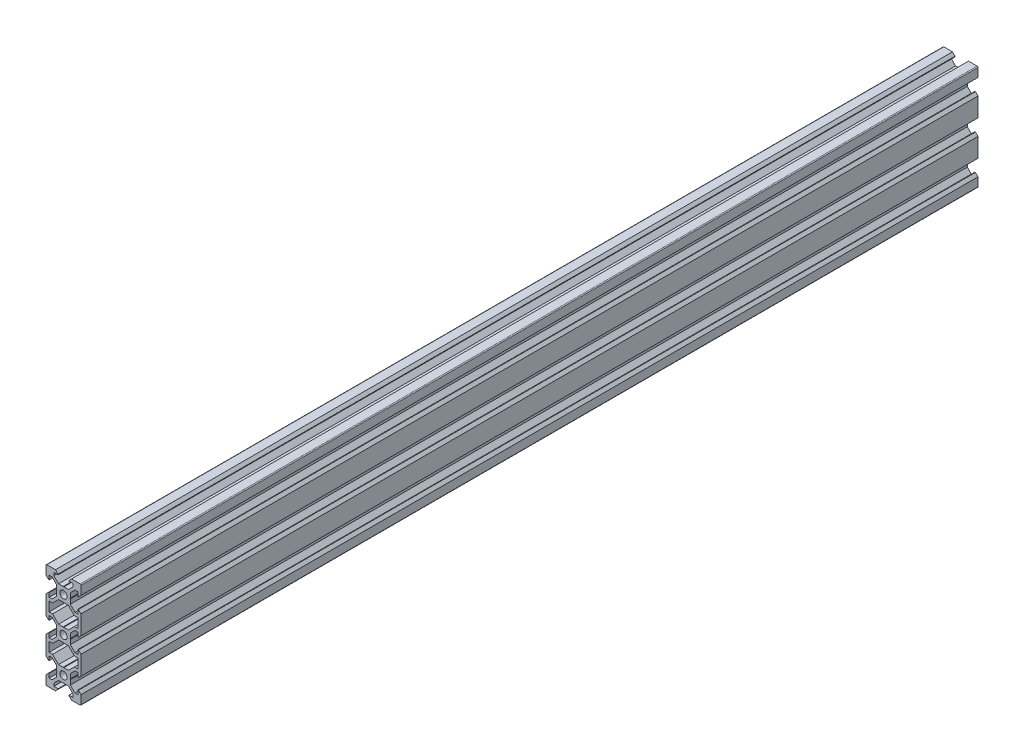
SolidWorks part; units mm, degrees
ref_plane "Plan de face" through (0, 0, 0) normal (0, 0, 1) x (1, 0, 0)
ref_plane "Plan de dessus" through (0, 0, 0) normal (0, 1, 0) x (1, 0, 0)
ref_plane "Plan de droite" through (0, 0, 0) normal (1, 0, 0) x (0, 0, -1)
ref_axis "Axe" through (0, 0, -13.782) along (0, 0, 1)
sketch "Esquisse1" plane through (0, 0, 0) normal (0, 0, 1) x (1, 0, 0)
  line L0 (0, 27.6392) -> (0, -27.6392) construction
  line L1 (-33.6074, 0) -> (33.6074, 0) construction
  line L2 (0, 0) -> (-22.2114, 22.2114) construction
  line L3 (-9.5, 10) -> (-4.58, 10)
  line L4 (-4.58, 10) -> (-3.125, 8.545)
  line L5 (-3.125, 8.545) -> (-3.125, 8.2)
  line L6 (-3.125, 8.2) -> (-5.5, 8.2)
  line L7 (-2.8393, 3.9) -> (-5.5, 6.5607)
  line L8 (-2.8393, 3.9) -> (-0.21, 3.9)
  line L9 (-5.5, 6.5607) -> (-5.5, 8.2)
  line L10 (0, 3.69) -> (0, 2.1)
  line L11 (-3.9, 2.8393) -> (-6.5607, 5.5)
  line L12 (-8.545, 3.125) -> (-8.2, 3.125)
  line L13 (-8.2, 3.125) -> (-8.2, 5.5)
  line L14 (-6.5607, 5.5) -> (-8.2, 5.5)
  line L15 (-10, 4.58) -> (-8.545, 3.125)
  line L16 (-10, 9.5) -> (-10, 4.58)
  line L17 (-0.21, 3.9) -> (0, 3.69)
  line L18 (-3.9, 2.8393) -> (-3.9, 0.21)
  line L19 (-6.2393, -12.7) -> (-8.2, -12.7)
  line L20 (-3.9, 0.21) -> (-3.69, 0)
  line L21 (-0.21, -3.9) -> (0, -3.69)
  line L22 (0, -3.69) -> (0, -2.1)
  line L23 (-6.5607, -5.5) -> (-8.2, -5.5)
  line L24 (-2.8393, -3.9) -> (-0.21, -3.9)
  line L25 (-8.545, -3.125) -> (-8.2, -3.125)
  line L26 (-10, -4.58) -> (-8.545, -3.125)
  line L27 (-8.2, -3.125) -> (-8.2, -5.5)
  line L28 (-2.8393, -3.9) -> (-6.2393, -7.3)
  line L29 (-3.9, -2.8393) -> (-6.5607, -5.5)
  line L30 (-3.9, -2.8393) -> (-3.9, -0.21)
  line L31 (-3.9, -0.21) -> (-3.69, 0)
  line L32 (-6.2393, -7.3) -> (-8.2, -7.3)
  line L33 (-8.2, -7.3) -> (-8.2, -12.7)
  line L34 (-8.2, -10) -> (-10, -10) construction
  line L35 (-10, -15.42) -> (-10, -4.58)
  line L36 (-3.9, -19.79) -> (-3.69, -20)
  line L37 (-3.9, -17.1607) -> (-3.9, -19.79)
  line L38 (-3.9, -17.1607) -> (-6.5607, -14.5)
  line L39 (-2.8393, -16.1) -> (-6.2393, -12.7)
  line L40 (-8.2, -16.875) -> (-8.2, -14.5)
  line L41 (-10, -15.42) -> (-8.545, -16.875)
  line L42 (-8.545, -16.875) -> (-8.2, -16.875)
  line L43 (-2.8393, -16.1) -> (-0.21, -16.1)
  line L44 (-6.5607, -14.5) -> (-8.2, -14.5)
  line L45 (0, -16.31) -> (0, -17.9)
  line L46 (-0.21, -16.1) -> (0, -16.31)
  line L47 (-8.2, -30) -> (-10, -30) construction
  line L48 (-3.69, -20) -> (0, -20) construction
  line L49 (-0.21, -23.9) -> (0, -23.69)
  line L50 (0, -23.69) -> (0, -22.1)
  line L51 (-6.5607, -25.5) -> (-8.2, -25.5)
  line L52 (-2.8393, -23.9) -> (-0.21, -23.9)
  line L53 (-8.545, -23.125) -> (-8.2, -23.125)
  line L54 (-10, -24.58) -> (-8.545, -23.125)
  line L55 (-8.2, -23.125) -> (-8.2, -25.5)
  line L56 (-2.8393, -23.9) -> (-6.2393, -27.3)
  line L57 (-3.9, -22.8393) -> (-6.5607, -25.5)
  line L58 (-3.9, -22.8393) -> (-3.9, -20.21)
  line L59 (-3.9, -20.21) -> (-3.69, -20)
  line L60 (-10, -24.58) -> (-10, -35.42)
  line L61 (-8.2, -32.7) -> (-8.2, -27.3)
  line L62 (-6.2393, -32.7) -> (-8.2, -32.7)
  line L63 (-3.9, -39.79) -> (-3.69, -40)
  line L64 (-3.9, -37.1607) -> (-3.9, -39.79)
  line L65 (-3.9, -37.1607) -> (-6.5607, -34.5)
  line L66 (-2.8393, -36.1) -> (-6.2393, -32.7)
  line L67 (-8.2, -36.875) -> (-8.2, -34.5)
  line L68 (-10, -35.42) -> (-8.545, -36.875)
  line L69 (-8.545, -36.875) -> (-8.2, -36.875)
  line L70 (-2.8393, -36.1) -> (-0.21, -36.1)
  line L71 (-6.5607, -34.5) -> (-8.2, -34.5)
  line L72 (0, -36.31) -> (0, -37.9)
  line L73 (-0.21, -36.1) -> (0, -36.31)
  line L74 (-3.9, -40.21) -> (-3.69, -40)
  line L75 (-6.2393, -27.3) -> (-8.2, -27.3)
  line L76 (-3.9, -42.8393) -> (-3.9, -40.21)
  line L77 (-0.21, -43.9) -> (0, -43.69)
  line L78 (-10, -49.5) -> (-10, -44.58)
  line L79 (-10, -44.58) -> (-8.545, -43.125)
  line L80 (-6.5607, -45.5) -> (-8.2, -45.5)
  line L81 (-8.2, -43.125) -> (-8.2, -45.5)
  line L82 (-8.545, -43.125) -> (-8.2, -43.125)
  line L83 (-3.9, -42.8393) -> (-6.5607, -45.5)
  line L84 (0, -43.69) -> (0, -42.1)
  line L85 (-5.5, -46.5607) -> (-5.5, -48.2)
  line L86 (-2.8393, -43.9) -> (-0.21, -43.9)
  line L87 (-2.8393, -43.9) -> (-5.5, -46.5607)
  line L88 (-3.125, -48.2) -> (-5.5, -48.2)
  line L89 (-3.125, -48.545) -> (-3.125, -48.2)
  line L90 (-4.58, -50) -> (-3.125, -48.545)
  line L91 (-9.5, -50) -> (-4.58, -50)
  arc A0 (0, -2.1) -> (0, 2.1) centre (0, 0) cw
  arc A1 (-9.5, 10) -> (-10, 9.5) centre (-9.5, 9.5) ccw
  arc A2 (0, -37.9) -> (0, -42.1) centre (0, -40) ccw
  arc A3 (-9.5, -50) -> (-10, -49.5) centre (-9.5, -49.5) cw
  arc A4 (0, -17.9) -> (0, -22.1) centre (0, -20) ccw
  point P4 (0, 0)
  point P7 (0, 0)
  point P30 (-10, 10)
  point P60 (0, -20)
  point P111 (-10, -50)
  dimension "D5" = 11
  dimension "D2" = 2.1
  dimension "D3" = 6.25
  dimension "D10" = 0.5
  dimension "D4" = 9.16
  dimension "D6" = 1.5
  dimension "D7" = 1.8
  dimension "D8" = 4.3
  dimension "D9" = 20
  dimension "D11" = 0.42
  dimension "D12" = 10
  dimension "D13" = 1.8
extrude "Boss.-Extru.1" add sketch "Esquisse1" along normal blind 512.76
sketch "Esquisse3" plane through (0, 0, 512.76) normal (0, 0, 1) x (1, 0, 0)
  line L0 (0, 0) -> (-9.8536, 9.8536) construction
  line L1 (-8.2, 8.2) -> (-8.2, 6.57)
  line L2 (-8.2, 6.57) -> (-7.54, 6.57)
  line L3 (-7.54, 6.57) -> (-6.57, 7.54)
  line L4 (-8.2, 3.125) -> (-8.2, 5.5) construction
  line L5 (-6.57, 8.2) -> (-6.57, 7.54)
  line L6 (-8.2, 8.2) -> (-6.57, 8.2)
  line L7 (-5.5, 6.5607) -> (-5.5, 8.2) construction
  line L8 (-3.69, -20) -> (0, -20) construction
  line L9 (-8.2, -48.2) -> (-6.57, -48.2)
  line L10 (-6.57, -48.2) -> (-6.57, -47.54)
  line L11 (-7.54, -46.57) -> (-6.57, -47.54)
  line L12 (-8.2, -46.57) -> (-7.54, -46.57)
  line L13 (-8.2, -48.2) -> (-8.2, -46.57)
  arc A0 (-9.5, 10) -> (-10, 9.5) centre (-9.5, 9.5) ccw construction
  point P13 (-7.055, 7.055)
  point P14 (-6.57, 7.87)
  point P26 (-7.055, -47.055)
  dimension "D1" = 1.07
extrude "Enlèv. mat.-Extru.1" [suppressed] cut sketch "Esquisse3" against normal through all
mirror "Symétrie1" about plane through (0, 3.69, 512.76) normal (-1, 0, 0) of "Enlèv. mat.-Extru.1", "Boss.-Extru.1"
